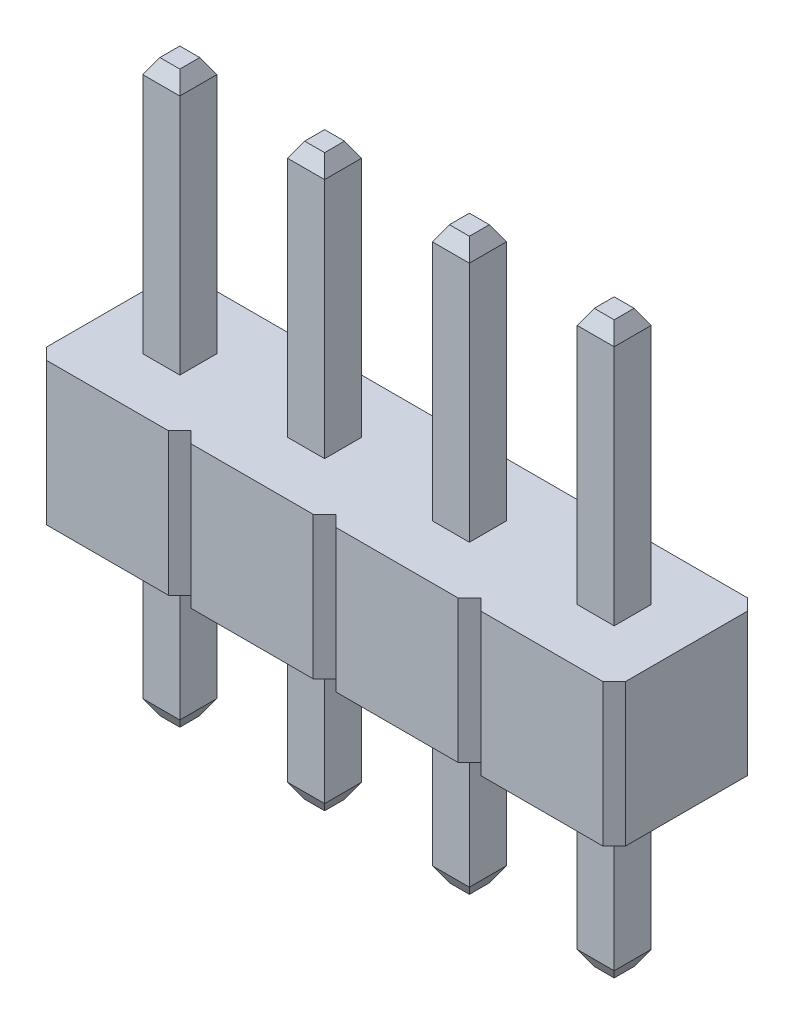
SolidWorks part; units mm, degrees
note: '?' marks a value the reader was unsure of.
ref_plane "Front Plane" through (0, 0, 0) normal (0, 0, 1) x (1, 0, 0)
ref_plane "Top Plane" through (0, 0, 0) normal (0, 1, 0) x (1, 0, 0)
ref_plane "Right Plane" through (0, 0, 0) normal (1, 0, 0) x (0, 0, -1)
sketch "Sketch1" plane through (0, 0, 0) normal (0, 1, 0) x (1, 0, 0)
  line L0 (-7.42, 1.27) -> (-7.62, 1.07)
  line L1 (-7.62, 1.27) -> (7.62, 1.27) construction
  line L2 (-7.62, 1.27) -> (-7.62, -1.27) construction
  line L3 (-7.62, -1.27) -> (7.62, -1.27) construction
  line L4 (7.62, 1.27) -> (7.62, -1.27) construction
  line L5 (-7.62, 1.27) -> (7.62, -1.27) construction
  line L6 (-7.62, -1.27) -> (7.62, 1.27) construction
  line L7 (-5.28, -1.27) -> (-7.42, -1.27)
  line L8 (-5.08, -1.07) -> (-5.08, 1.07)
  line L9 (-5.28, 1.27) -> (-7.42, 1.27)
  line L10 (-7.62, -1.07) -> (-7.62, 1.07)
  line L11 (-5.08, -1.27) -> (-7.62, 1.27) construction
  line L12 (-5.08, 1.27) -> (-7.62, -1.27) construction
  line L13 (-5.08, 1.07) -> (-5.28, 1.27)
  line L14 (-7.42, -1.27) -> (-7.62, -1.07)
  line L15 (-5.08, -1.07) -> (-5.28, -1.27)
  point P0 (0, 0)
  point P6 (-6.35, 0)
  dimension "D1" = 15.24
  dimension "D2" = 2.54
extrude "Boss-Extrude1" add sketch "Sketch1" along normal blind 2.5
ref_plane "Plane1" through (0, -3, 0) normal (0, 1, 0) x (1, 0, 0)
sketch "Sketch3" plane through (0, -3, 0) normal (0, 1, 0) x (1, 0, 0)
  line L0 (-7.52, -1.17) -> (-5.18, 1.17) construction
  line L1 (-7.62, -1.07) -> (-7.42, -1.27) construction
  line L2 (-5.08, 1.07) -> (-5.28, 1.27) construction
  line L4 (-6.675, 0.325) -> (-6.025, 0.325)
  line L5 (-6.675, 0.325) -> (-6.675, -0.325)
  line L6 (-6.675, -0.325) -> (-6.025, -0.325)
  line L7 (-6.025, 0.325) -> (-6.025, -0.325)
  line L8 (-6.675, 0.325) -> (-6.025, -0.325) construction
  line L9 (-6.675, -0.325) -> (-6.025, 0.325) construction
  circle A0 centre (-6.35, 0) radius 0.325 construction
  dimension "D1" = 0.65
extrude "Boss-Extrude2" add sketch "Sketch3" along normal blind 10
chamfer "Chamfer2" distance 0.15 angle 60 4 edges at (-6.35, -3, -0.325) (-6.675, -3, 0) (-6.35, -3, 0.325) (-6.025, -3, 0)
ref_plane "Plane2" through (0, 1.25, 0) normal (0, -1, 0) x (-1, 0, 0)
chamfer "Chamfer3" distance 0.15 angle 60 4 edges at (-6.35, 7, 0.325) (-6.675, 7, 0) (-6.35, 7, -0.325) (-6.025, 7, 0)
pattern_linear "LPattern2" count 4 spacing 2.54 along (1, 0, 0) of "Boss-Extrude1", "Boss-Extrude2", "Chamfer2", "Chamfer3"
ref_plane "Plane3" through (-6.35, 0, 0) normal (-1, 0, 0) x (0, 0, 1)
ref_plane "Plane4" through (0, 0, 0) normal (0, 0, -1) x (-1, 0, 0)
ref_axis "Axis1" through (-6.35, 6.9522, 0) along (0, -1, 0)?
